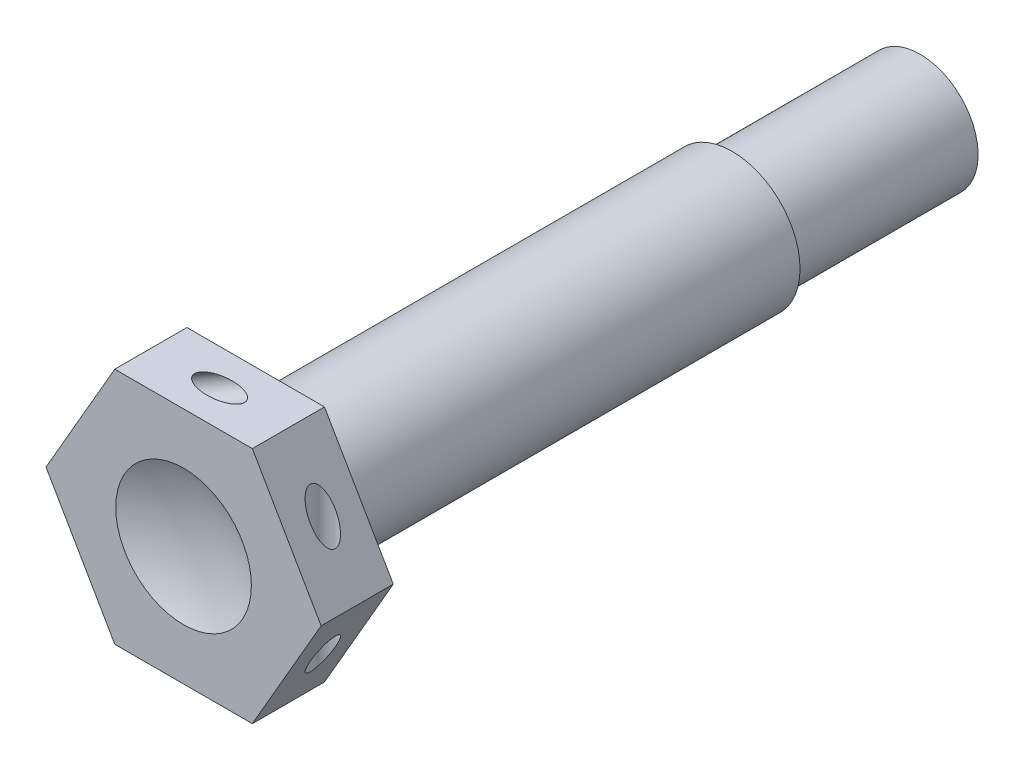
SolidWorks part; units mm, degrees
material "Alloy Steel"
ref_plane "Plane1" through (0, 0, 0) normal (0, 0, 1) x (1, 0, 0)
ref_plane "Plane2" through (0, 0, 0) normal (0, 1, 0) x (1, 0, 0)
ref_plane "Plane3" through (0, 0, 0) normal (1, 0, 0) x (0, 0, -1)
ref_axis "Axis1" through (-83.9706, 0, 0) along (1, 0, 0)
ref_axis "Axis2" through (0, 0, -32.7057) along (0, 0, 1)
ref_axis "Axis3" through (0, 6.1119, 0) along (0, -1, 0)
sketch "Sketch1" plane through (0, 0, 0) normal (0, 0, 1) x (1, 0, 0)
  line L1 (3.2079, 5.5562) -> (-3.2079, 5.5562)
  line L2 (-3.2079, 5.5562) -> (-6.4158, 0)
  line L3 (-6.4158, 0) -> (-3.2079, -5.5563)
  line L4 (-3.2079, -5.5563) -> (3.2079, -5.5563)
  line L5 (3.2079, -5.5563) -> (6.4158, 0)
  line L6 (6.4158, 0) -> (3.2079, 5.5562)
  circle A0 centre (0, 0) radius 5.5562 construction
  dimension "D1" = 11.1125
extrude "Boss-Extrude1" add sketch "Sketch1" along normal blind 3.3655
sketch "Sketch2" plane through (0, 0, 0) normal (0, 0, -1) x (-1, 0, 0)
  circle A0 centre (0, 0) radius 3.1623
  dimension "D1" = 6.3246
extrude "Boss-Extrude2" add sketch "Sketch2" along normal blind 22.225
sketch "Sketch3" plane through (0, 0, -22.225) normal (0, 0, -1) x (-1, 0, 0)
  circle A0 centre (0, 0) radius 2.7051
  dimension "D1" = 5.4102
extrude "Boss-Extrude3" add sketch "Sketch3" along normal blind 8.763
sketch "Sketch4" plane through (0, 0, 0) normal (1, 0, 0) x (0, 0, -1)
  line L0 (-3.3655, 0) -> (-3.3655, 3.1623)
  line L1 (-3.3655, 0) -> (-3.3655, 5.5562) construction
  line L2 (-3.3655, 0) -> (0, 0) construction
  line L3 (-3.3655, 0) -> (-2.6644, 0)
  line L4 (-2.6644, 0) -> (-2.6644, 2.4426) construction
  line L5 (-3.3655, 3.1623) -> (-3.5111, 3.4745) construction
  arc A0 (-3.3655, 3.1623) -> (-2.6644, 0) centre (-10.1471, 0) cw
  dimension "D1" = 3.1623
  dimension "D2" = 25
revolve "Cut-Revolve1" cut sketch "Sketch4" angle 360 about L3
sketch "Sketch5" plane through (0, 0, 0) normal (0, 1, 0) x (1, 0, 0)
  line L0 (4.8119, -1.6827) -> (6.4158, -1.6827) construction
  line L1 (6.4158, -3.3655) -> (6.4158, 0) construction
  line L2 (4.8119, -1.6827) -> (3.2079, -1.6827) construction
  line L4 (3.2079, -3.3655) -> (3.2079, 0) construction
  circle A0 centre (4.8119, -1.6827) radius 0.5842
  dimension "D1" = 1.1684
extrude "Cut-Extrude1" cut sketch "Sketch5" against normal through all and the other way through all
pattern_circular "CirPattern1" count 3 over 360 about axis through (0, 0, -32.7057) along (0, 0, 1) of "Cut-Extrude1"
equation "\"hexwid\"= 0.4375"
equation "\"hexht\"= 0.1325"
equation "\"gripd\"= 0.249"
equation "\"threadd\"= 0.213"
equation "\"threadlen\"= 0.37"
equation "\"wd\"= 0.046"
equation "\"griplen\"= 0.875"
equation "\"D1@Sketch1\" = \"hexwid\""
equation "\"D1@Boss-Extrude1\" = \"hexht\""
equation "\"D1@Sketch2\" = \"gripd\""
equation "\"D1@Boss-Extrude2\" = \"griplen\""
equation "\"D1@Sketch3\" = \"threadd\""
equation "\"D1@Sketch4\" = \"gripd\"/2"
equation "\"D2@Sketch4\" = 25deg"
equation "\"D1@Cut-Revolve1\" = 360deg"
equation "\"D1@Sketch5\" = \"wd\""
equation "\"D3@CirPattern1\" = 360deg"
equation "\"D1@CirPattern1\" = 3"
